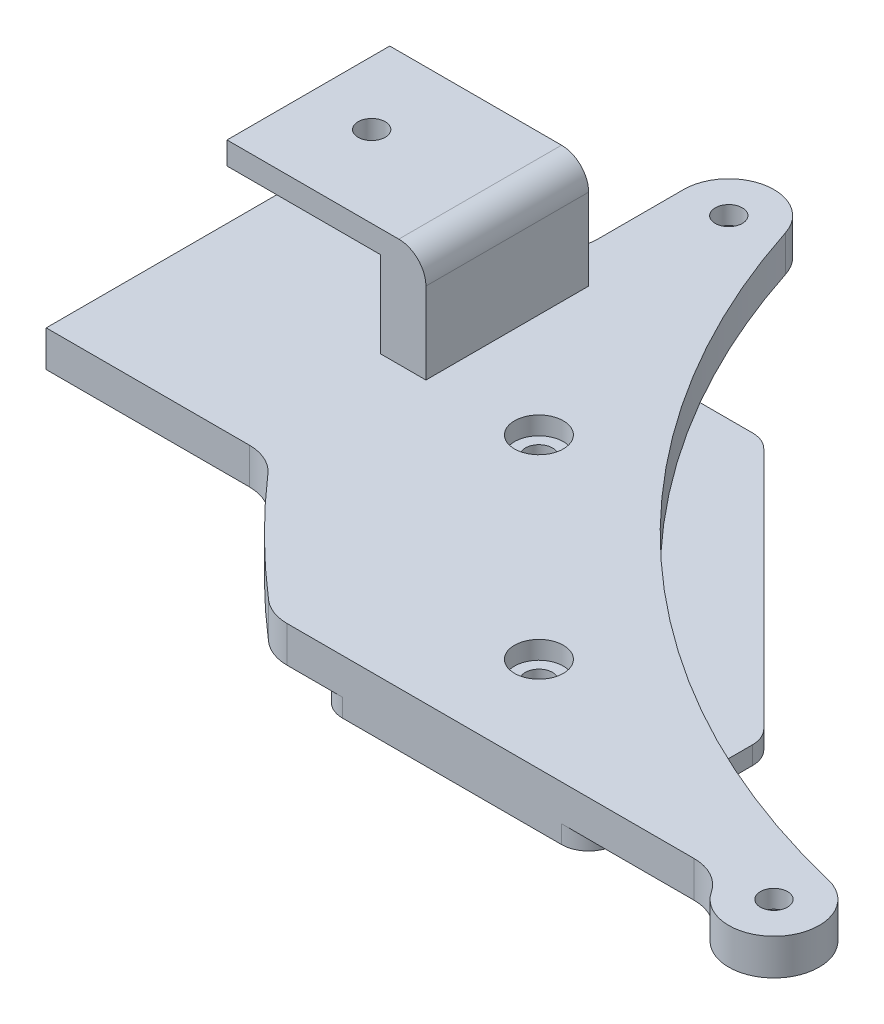
SolidWorks part; units mm, degrees
ref_plane "Alzado" through (0, 0, 0) normal (0, 0, 1) x (1, 0, 0)
ref_plane "Planta" through (0, 0, 0) normal (0, 1, 0) x (1, 0, 0)
ref_plane "Vista lateral" through (0, 0, 0) normal (1, 0, 0) x (0, 0, -1)
sketch "Croquis2" plane through (0, 0, 0) normal (0, 1, 0) x (1, 0, 0)
  line L1 (5, 43) -> (16, 43)
  line L2 (5, 43) -> (5, 21)
  line L3 (5, 21) -> (16, 21)
  line L4 (16, 43) -> (16, 21)
  line L5 (21, 16) -> (43, 16)
  line L6 (21, 16) -> (21, 5)
  line L7 (21, 5) -> (43, 5)
  line L8 (43, 16) -> (43, 5)
  dimension "D1" = 11
  dimension "D2" = 22
  dimension "D3" = 38
  dimension "D4" = 38
  dimension "D5" = 5
  dimension "D6" = 5
sketch "Croquis1" plane through (0, 0, 0) normal (0, 1, 0) x (1, 0, 0)
  line L0 (3, 48) -> (18.1299, 48)
  line L1 (20.2513, 47.1213) -> (47.1213, 20.2513)
  line L2 (48, 18.1299) -> (48, 3)
  line L3 (45, 0) -> (20.7846, 0)
  line L4 (0, 45) -> (0, 20.7846)
  line L7 (43, 16) -> (43, 5) construction
  arc A0 (17.8154, 2.5714) -> (2.5714, 17.8154) centre (0, 0) ccw
  arc A1 (0, 20.7846) -> (2.5714, 17.8154) centre (3, 20.7846) ccw
  arc A2 (20.7846, 0) -> (17.8154, 2.5714) centre (20.7846, 3) cw
  arc A3 (48, 3) -> (45, 0) centre (45, 3) cw
  arc A4 (47.1213, 20.2513) -> (48, 18.1299) centre (45, 18.1299) cw
  arc A5 (18.1299, 48) -> (20.2513, 47.1213) centre (18.1299, 45) cw
  arc A6 (3, 48) -> (0, 45) centre (3, 45) ccw
  point P9 (0, 18)
  point P12 (18, 0)
  dimension "D1" = 3
  dimension "D3" = 5
  dimension "D4" = 38
  dimension "D2" = 18
extrude "Saliente-Extruir2" add sketch "Croquis1" against normal blind 2
sketch "Croquis3" plane through (0, -2, 0) normal (0, -1, 0) x (-1, 0, 0)
  line L0 (0, 0) -> (69.0794, 0) construction
  line L1 (0, 0) -> (0, 64) construction
  line L2 (0, 64) -> (68, 1)
  line L3 (0, 0) -> (6.8, 0)
  line L4 (0, 0) -> (0, 6.3)
  line L5 (0, 6.3) -> (6.8, 0)
  line L6 (68, 1) -> (0, 1) construction
  line L7 (0, 1) -> (0, 64) construction
  line L8 (0, 0) -> (32, 32) construction
  line L9 (32, 32) -> (0, 64) construction
  line L10 (-16, 43) -> (21, 43) construction
  line L11 (-16, 21) -> (21, 21) construction
  circle A0 centre (68, 1) radius 6.6832
  circle A1 centre (0, 64) radius 7.3712
  dimension "D1" = 6.3
  dimension "D2" = 6.8
  dimension "D3" = 68
  dimension "D5" = 45
  dimension "D6" = 45
sketch "Croquis5" plane through (0, 0, 0) normal (0, 1, 0) x (1, 0, 0)
  line L0 (0, 63.5) -> (0, 0.5) construction
  line L1 (0, 0.5) -> (68, 0.5) construction
  line L2 (5, 32) -> (0, 32) construction
  line L3 (5, 43) -> (5, 21) construction
  dimension "D1" = 63
  dimension "D2" = 68
  dimension "D3" = 5
sketch "Croquis4" plane through (0, 0, 0) normal (0, 1, 0) x (1, 0, 0)
  line L2 (14.6484, 0) -> (59.6484, 0)
  line L3 (-5, 63.5) -> (-5, 54)
  line L4 (-10, 49) -> (-27, 49)
  line L5 (-27, 49) -> (-27, 15)
  line L6 (-27, 15) -> (-4.5336, 15)
  line L8 (0, 32) -> (-27, 32) construction
  circle A0 centre (0, 63.5) radius 1.5
  circle A1 centre (68, 0.5) radius 1.5
  arc A2 (4.7557, 65.0438) -> (-5, 63.5) centre (0, 63.5) ccw
  arc A3 (63.8242, -2.25) -> (69.1768, 5.3595) centre (68, 0.5) ccw
  arc A4 (63.8242, -2.25) -> (59.6484, 0) centre (59.6484, -5) ccw
  arc A5 (14.6484, 0) -> (11.3838, 1.2128) centre (14.6484, 5) cw
  arc A6 (-4.5336, 15) -> (-0.7668, 13.288) centre (-4.5336, 10) cw
  arc A7 (-5, 54) -> (-10, 49) centre (-10, 54) cw
  arc A8 (4.7557, 65.0438) -> (69.1768, 5.3595) centre (90.3585, 92.8314) ccw
  arc A9 (-0.7668, 13.288) -> (11.3838, 1.2128) centre (90.3585, 92.8314) ccw
  point P26 (18, 0)
  dimension "D1" = 3
  dimension "D2" = 3
  dimension "D3" = 5
  dimension "D6" = 5
  dimension "D7" = 90
  dimension "D4" = 34
  dimension "D5" = 27
  dimension "D8" = 45
extrude "Saliente-Extruir3" add sketch "Croquis4" along normal blind 4
sketch "Croquis6" plane through (0, -2, 0) normal (0, -1, 0) x (1, 0, 0)
  line L0 (5, -43) -> (5, -21) construction
  line L1 (5, -21) -> (16, -21) construction
  line L2 (21, -16) -> (21, -5) construction
  line L3 (21, -5) -> (43, -5) construction
  circle A0 centre (10.5, -32) radius 1.5
  circle A1 centre (32, -10.5) radius 1.5
  dimension "D5" = 3
  dimension "D1" = 5.5
  dimension "D2" = 11
  dimension "D3" = 11
  dimension "D4" = 5.5
extrude "Cortar-Extruir1" cut sketch "Croquis6" against normal blind 44
sketch "Croquis7" plane through (0, 4, 0) normal (0, 1, 0) x (1, 0, 0)
  circle A0 centre (10.5, 32) radius 2.7
  circle A1 centre (32, 10.5) radius 2.7
  dimension "D1" = 5.4
extrude "Cortar-Extruir2" cut sketch "Croquis7" against normal blind 2
sketch "Croquis8" plane through (0, 0, 0) normal (0, -1, 0) x (1, 0, 0)
  line L1 (0, -60.3246) -> (-2.75, -61.9123)
  line L2 (-2.75, -61.9123) -> (-2.75, -65.0877)
  line L3 (-2.75, -65.0877) -> (0, -66.6754)
  line L4 (0, -66.6754) -> (2.75, -65.0877)
  line L5 (2.75, -65.0877) -> (2.75, -61.9123)
  line L6 (2.75, -61.9123) -> (0, -60.3246)
  circle A0 centre (0, -63.5) radius 2.75 construction
  dimension "D1" = 5.5
extrude "Cortar-Extruir3" cut sketch "Croquis8" against normal blind 2
sketch "Croquis9" plane through (0, 0, 0) normal (0, -1, 0) x (1, 0, 0)
  line L1 (64.8246, -0.5) -> (66.4123, -3.25)
  line L2 (66.4123, -3.25) -> (69.5877, -3.25)
  line L3 (69.5877, -3.25) -> (71.1754, -0.5)
  line L4 (71.1754, -0.5) -> (69.5877, 2.25)
  line L5 (69.5877, 2.25) -> (66.4123, 2.25)
  line L6 (66.4123, 2.25) -> (64.8246, -0.5)
  circle A0 centre (68, -0.5) radius 2.75 construction
  dimension "D1" = 5.5
extrude "Cortar-Extruir4" cut sketch "Croquis9" against normal blind 2
sketch "Croquis10" plane through (0, 4, 0) normal (0, 1, 0) x (1, 0, 0)
  line L0 (-27, 49) -> (-27, 15) construction
  line L1 (-6, 49) -> (-1, 49)
  line L2 (-6, 49) -> (-6, 31)
  line L3 (-6, 31) -> (-1, 31)
  line L4 (-1, 49) -> (-1, 31)
  dimension "D1" = 21
  dimension "D2" = 5
  dimension "D3" = 18
  dimension "D4" = 0
extrude "Saliente-Extruir4" add sketch "Croquis10" along normal blind 2
sketch "Croquis11" plane through (0, 0, -31) normal (0, 0, 1) x (1, 0, 0)
  line L0 (-6, 4) -> (-6, 13.5)
  line L1 (-6, 13.5) -> (-23, 13.5)
  line L2 (-23, 13.5) -> (-23, 16)
  line L3 (-23, 16) -> (-4, 16)
  line L4 (-1, 13) -> (-1, 4)
  line L5 (-6, 4) -> (-1, 4)
  arc A0 (-4, 16) -> (-1, 13) centre (-4, 13) cw
  point P10 (-1, 16)
  dimension "D3" = 3
  dimension "D1" = 9.5
  dimension "D2" = 12
  dimension "D4" = 17
extrude "Saliente-Extruir5" add sketch "Croquis11" against normal up to vertex (18 mm away) up to point (-6, 6, -49)
sketch "Croquis12" plane through (0, 16, 0) normal (0, 1, 0) x (1, 0, 0)
  line L0 (-23, 49) -> (-23, 31) construction
  line L1 (-4, 31) -> (-23, 31) construction
  circle A0 centre (-16, 40) radius 1.5
  dimension "D1" = 3
  dimension "D2" = 7
  dimension "D3" = 9
extrude "Cortar-Extruir5" cut sketch "Croquis12" against normal blind 5
ref_axis "Eje1" through (10.5, 41.5114, -32) along (0, -1, 0)
ref_axis "Eje2" through (32, 29.3572, -10.5) along (0, -1, 0)
